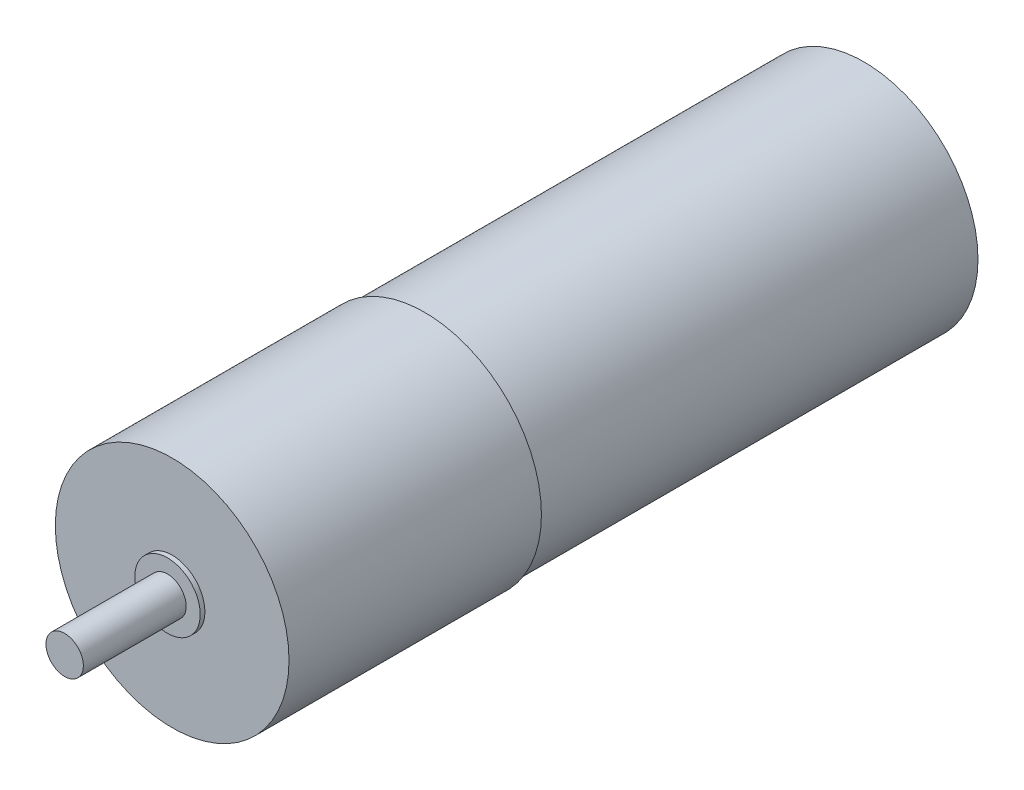
SolidWorks part; units mm, degrees
ref_plane "Front Plane" through (0, 0, 0) normal (0, 0, 1) x (1, 0, 0)
ref_plane "Top Plane" through (0, 0, 0) normal (0, 1, 0) x (1, 0, 0)
ref_plane "Right Plane" through (0, 0, 0) normal (1, 0, 0) x (0, 0, -1)
sketch "Sketch3" plane through (0, 0, 0) normal (0, 0, 1) x (1, 0, 0)
  circle A2 centre (0, 0) radius 12.2
  dimension "D1" = 24.4
extrude "Boss-Extrude1" add sketch "Sketch3" along normal blind 47
sketch "Sketch4" plane through (0, 0, 47) normal (0, 0, 1) x (1, 0, 0)
  circle A0 centre (0, 0) radius 12.5
  dimension "D1" = 25
extrude "Boss-Extrude2" add sketch "Sketch4" along normal blind 27
sketch "Sketch5" plane through (0, 0, 74) normal (0, 0, 1) x (1, 0, 0)
  circle A0 centre (0, 0) radius 3.5
  dimension "D1" = 7
extrude "Boss-Extrude3" add sketch "Sketch5" along normal blind 0.5
sketch "Sketch6" plane through (0, 0, 74.5) normal (0, 0, 1) x (1, 0, 0)
  circle A0 centre (0, 0) radius 2
  dimension "D1" = 4
extrude "Boss-Extrude4" add sketch "Sketch6" along normal blind 11 contours A0
